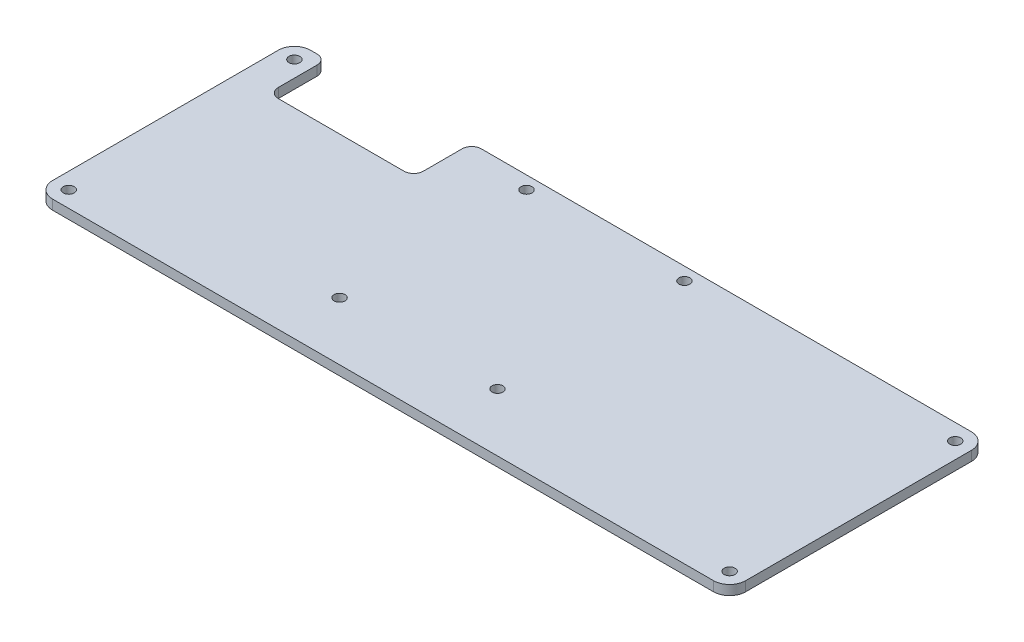
SolidWorks part; units mm, degrees
ref_plane "Front" through (0, 0, 0) normal (0, 0, 1) x (1, 0, 0)
ref_plane "Top" through (0, 0, 0) normal (0, 1, 0) x (1, 0, 0)
ref_plane "Right" through (0, 0, 0) normal (1, 0, 0) x (0, 0, -1)
sketch "Esquisse1" plane through (0, 0, 0) normal (0, 1, 0) x (1, 0, 0)
  line L1 (0, 0) -> (215, 0)
  line L2 (0, 0) -> (0, 80)
  line L3 (0, 80) -> (215, 80)
  line L4 (215, 0) -> (215, 80)
  dimension "D1" = 215
  dimension "D2" = 80
extrude "Boss.-Extru.1" add sketch "Esquisse1" along normal blind 3
fillet "Congé1" radius 5 4 edges at (0, 1.5, -80) (0, 1.5, 0) (215, 1.5, -80) (215, 1.5, 0)
sketch "Esquisse2" plane through (0, 3, 0) normal (0, 1, 0) x (1, 0, 0)
  line L0 (0, 75) -> (0, 5) construction
  line L1 (210, 80) -> (5, 80) construction
  line L2 (5, 0) -> (210, 0) construction
  line L3 (215, 5) -> (215, 75) construction
  line L5 (10, 80) -> (55, 80)
  line L6 (10, 80) -> (10, 62)
  line L7 (10, 62) -> (55, 62)
  line L8 (55, 80) -> (55, 62)
  circle A0 centre (5, 75) radius 1
  circle A1 centre (210, 75) radius 1
  circle A2 centre (210, 5) radius 1
  circle A3 centre (5, 5) radius 1
  dimension "D9" = 2
  dimension "D10" = 2
  dimension "D11" = 2
  dimension "D12" = 2
  dimension "D1" = 5
  dimension "D2" = 5
  dimension "D3" = 5
  dimension "D4" = 5
  dimension "D5" = 5
  dimension "D6" = 5
  dimension "D7" = 5
  dimension "D8" = 5
  dimension "D13" = 10
  dimension "D14" = 45
  dimension "D15" = 18
extrude "Enlèv. mat.-Extru.1" cut sketch "Esquisse2" against normal through all
hole_wizard "Dégagement M31" positions "Esquisse3" profile "Esquisse4" hole size "M3" standard "ISO"
sketch "Esquisse3" plane through (0, 3, 0) normal (0, 1, 0) x (1, 0, 0)
  point P0 (210, 5)
  point P3 (5, 5)
  point P6 (5, 75)
  point P9 (210, 75)
sketch "Esquisse4" plane through (210, 3, -5) normal (1, 0, 0) x (0, 0, 1)
  line L0 (0, 0) -> (0, 11.0215)
  line L1 (0, 11.0215) -> (1.7, 10)
  line L2 (1.7, 10) -> (1.7, 0)
  line L5 (1.7, 0) -> (0, 0)
  line L10 (0, 11.0215) -> (-1.7, 10) construction
  line L11 (0, -6.35) -> (0, 107.95) construction
  dimension "Diamètre du perçage" = 3.4
  dimension "Profondeur du perçage" = 10
  dimension "Angle de pointe" = 118
fillet "Congé2" radius 3 4 edges at (55, 1.5, -62) (55, 1.5, -80) (10, 1.5, -80) (10, 1.5, -62)
sketch "Esquisse5" plane through (0, 3, 0) normal (0, 1, 0) x (1, 0, 0)
  line L0 (215, 5) -> (215, 75) construction
  line L1 (5, 0) -> (210, 0) construction
  line L3 (76, 76) -> (125, 76) construction
  line L4 (76, 76) -> (76, 18) construction
  line L5 (76, 18) -> (125, 18) construction
  line L6 (125, 76) -> (125, 18) construction
  circle A0 centre (125, 18) radius 1
  circle A1 centre (125, 76) radius 1
  circle A2 centre (76, 76) radius 1
  circle A3 centre (76, 18) radius 1
  dimension "D7" = 2
  dimension "D8" = 2
  dimension "D9" = 2
  dimension "D10" = 2
  dimension "D2" = 18
  dimension "D4" = 49
  dimension "D5" = 58
  dimension "D11" = 90
extrude "Enlèv. mat.-Extru.2" cut sketch "Esquisse5" against normal up to surface (3 mm away) up to face at (210, 0, -6.7)
hole_wizard "Dégagement M32" positions "Esquisse7" profile "Esquisse8" hole size "M3" standard "ISO" end condition through all
sketch "Esquisse7" plane through (0, 3, 0) normal (0, 1, 0) x (1, 0, 0)
  point P0 (125, 76)
  point P3 (76, 76)
  point P6 (76, 18)
  point P9 (125, 18)
sketch "Esquisse8" plane through (125, 3, -76) normal (1, 0, 0) x (0, 0, 1)
  line L0 (0, 0) -> (0, 3)
  line L1 (0, 3) -> (1.7, 3)
  line L2 (1.7, 3) -> (1.7, 0)
  line L5 (1.7, 0) -> (0, 0)
  line L11 (0, -6.35) -> (0, 107.95) construction
  dimension "Diamètre du perçage jusqu'au prochain" = 3.4
  dimension "Profondeur du perçage jusqu'au prochain" = 3
